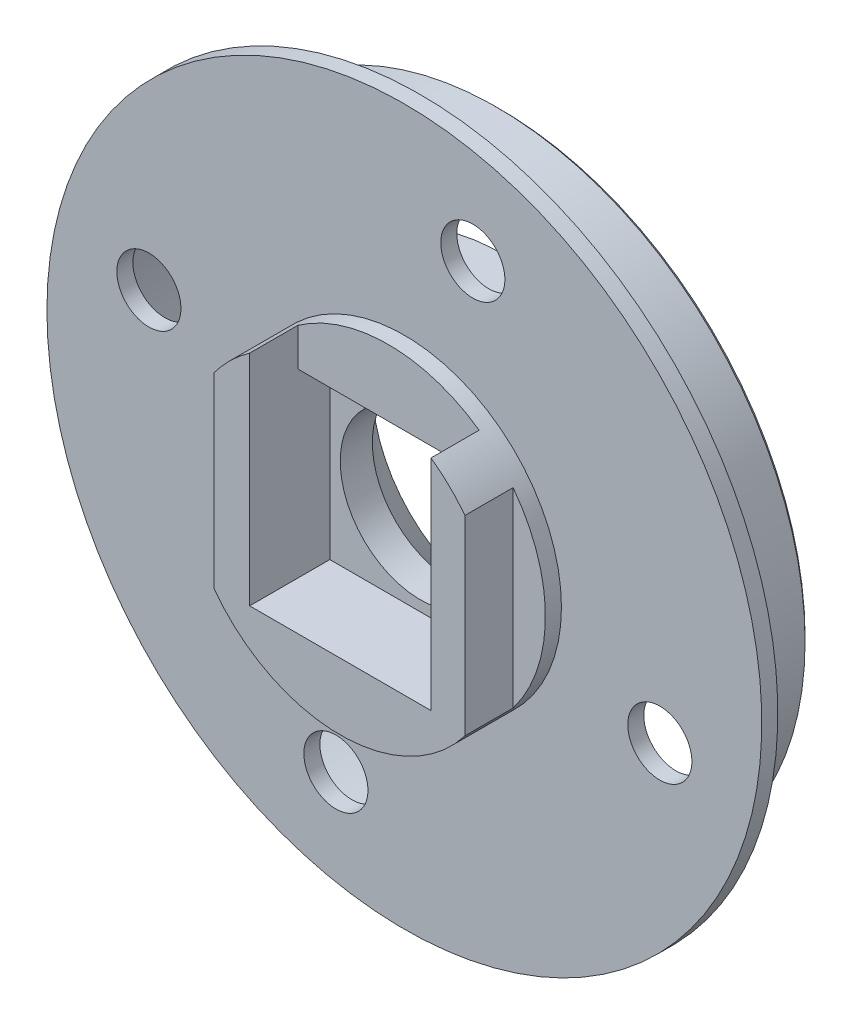
SolidWorks part; units mm, degrees
ref_plane "Front Plane" through (0, 0, 0) normal (0, 0, 1) x (1, 0, 0)
ref_plane "Top Plane" through (0, 0, 0) normal (0, 1, 0) x (1, 0, 0)
ref_plane "Right Plane" through (0, 0, 0) normal (1, 0, 0) x (0, 0, -1)
sketch "Sketch1" plane through (0, 0, 0) normal (0, 0, 1) x (1, 0, 0)
  circle A0 centre (0, 0) radius 9.8
  circle A1 centre (0, 0) radius 5
  dimension "D1" = 19.6
  dimension "D2" = 10
extrude "Boss-Extrude1" add sketch "Sketch1" along normal blind 10
sketch "Sketch2" plane through (0, 0, 10) normal (0, 0, 1) x (1, 0, 0)
  line L1 (-5.65, 5.65) -> (5.65, 5.65)
  line L2 (-5.65, 5.65) -> (-5.65, -5.65)
  line L3 (-5.65, -5.65) -> (5.65, -5.65)
  line L4 (5.65, 5.65) -> (5.65, -5.65)
  point P4 (5.65, 0)
  point P5 (0, 5.65)
  dimension "D1" = 11.3
  dimension "D2" = 11.3
extrude "Cut-Extrude1" cut sketch "Sketch2" against normal blind 5
sketch "Sketch3" plane through (0, 0, 10) normal (0, 0, 1) x (1, 0, 0)
  line L1 (-5.65, 5.65) -> (5.6634, 5.65)
  line L2 (-5.65, 5.65) -> (-5.65, 10.3571)
  line L3 (-5.65, 10.3571) -> (5.6634, 10.3571)
  line L4 (5.6634, 5.65) -> (5.6634, 10.3571)
extrude "Cut-Extrude2" cut sketch "Sketch3" against normal blind 3
sketch "Sketch4" plane through (0, 0, 10) normal (0, 0, 1) x (1, 0, 0)
  line L1 (-13.2922, 9.0382) -> (-7.8874, 9.0382)
  line L2 (-13.2922, 9.0382) -> (-13.2922, -9.0382)
  line L3 (-13.2922, -9.0382) -> (-7.8874, -9.0382)
  line L4 (-7.8874, 9.0382) -> (-7.8874, -9.0382)
  line L5 (13.4474, 9.0382) -> (7.784, 9.0382)
  line L6 (13.4474, 9.0382) -> (13.4474, -8.9089)
  line L7 (13.4474, -8.9089) -> (7.784, -8.9089)
  line L8 (7.784, 9.0382) -> (7.784, -8.9089)
extrude "Cut-Extrude3" cut sketch "Sketch4" against normal blind 3
chamfer "Chamfer1" distance 3 angle 45 1 edges at (5, 0, 0)
ref_plane "Plane1" through (0, 0, 5) normal (0, 0, -1) x (-1, 0, 0)
sketch "Sketch5" plane through (0, 0, 5) normal (0, 0, -1) x (-1, 0, 0)
  circle A0 centre (0, 0) radius 9.8
  circle A1 centre (0, 0) radius 22.3
  dimension "D1" = 12.5
extrude "Boss-Extrude2" add sketch "Sketch5" against normal blind 1
sketch "Sketch6" plane through (0, 0, 5) normal (0, 0, -1) x (-1, 0, 0)
  circle A0 centre (0, 0) radius 9.8
  circle A1 centre (0, 0) radius 11.25
  dimension "D1" = 22.5
extrude "Boss-Extrude3" add sketch "Sketch6" along normal up to surface (5 mm away) up to face at (8, 0, 0)
sketch "Sketch7" plane through (0, 0, 5) normal (0, 0, -1) x (-1, 0, 0)
  circle A0 centre (0, 0) radius 18.75
  circle A1 centre (0, 0) radius 19.25
  dimension "D1" = 37.5
  dimension "D2" = 38.5
extrude "Boss-Extrude4" add sketch "Sketch7" along normal up to surface (5 mm away) up to face at (8, 0, 0)
chamfer "Chamfer2" distance 0.25 angle 45 1 edges at (19.25, 0, 0)
sketch "Sketch8" plane through (0, 0, 5) normal (0, 0, -1) x (-1, 0, 0)
  circle A0 centre (-4.2705, 15.9378) radius 2
  point P2 (0, 0)
  point P5 (-1.354, 12.8626)
  dimension "D1" = 4
  dimension "D2" = 15.9378
  dimension "D3" = 4.2705
extrude "Cut-Extrude4" cut sketch "Sketch8" against normal through all
ref_axis "Axis1" through (0, 0, 10.5849) along (0, 0, -1)
pattern_circular "CirPattern1" count 4 over 360 about axis through (0, 0, 10.5849) along (0, 0, -1) of "Cut-Extrude4"
